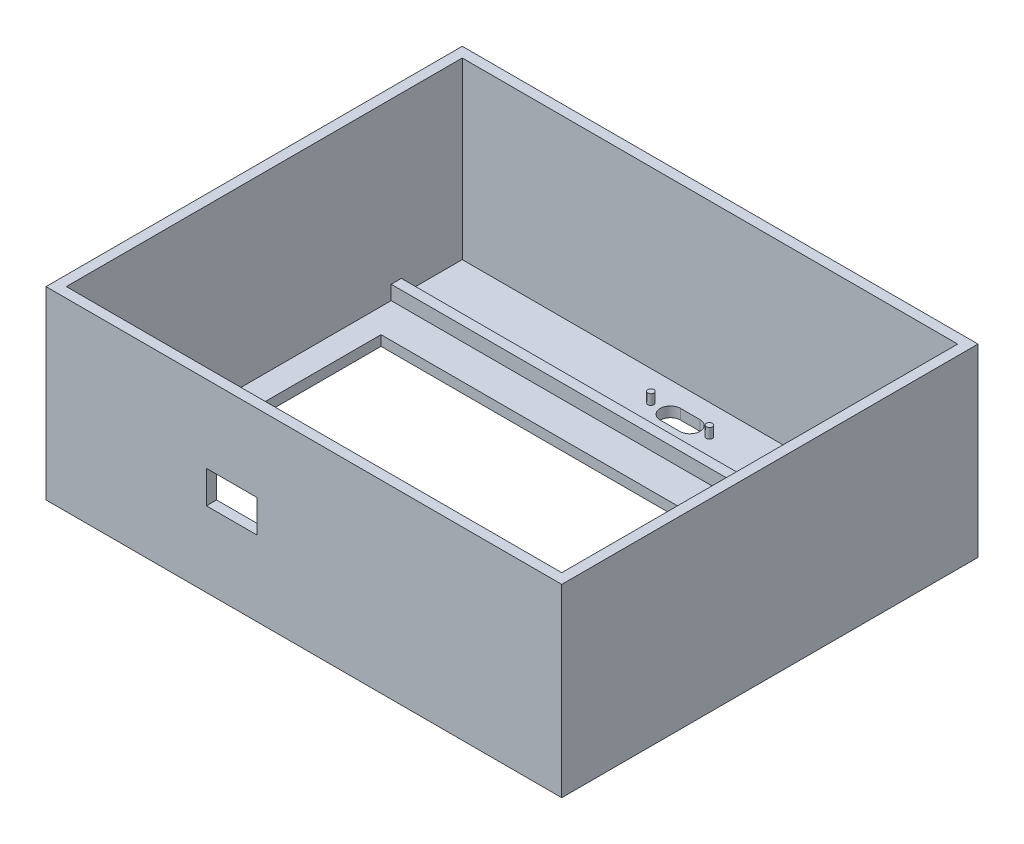
SolidWorks part; units mm, degrees
ref_plane "Front Plane" through (0, 0, 0) normal (0, 0, 1) x (1, 0, 0)
ref_plane "Top Plane" through (0, 0, 0) normal (0, 1, 0) x (1, 0, 0)
ref_plane "Right Plane" through (0, 0, 0) normal (1, 0, 0) x (0, 0, -1)
sketch "Sketch1" plane through (0, 0, 0) normal (0, 1, 0) x (1, 0, 0)
  line L1 (0, 0) -> (127, 0)
  line L2 (0, 0) -> (0, 85)
  line L3 (0, 85) -> (127, 85)
  line L4 (127, 0) -> (127, 85)
extrude "Boss-Extrude1" add sketch "Sketch1" along normal blind 2.5
sketch "Sketch2" plane through (0, 2.5, 0) normal (0, 1, 0) x (1, 0, 0)
  line L0 (0, 85) -> (127, 85)
  line L1 (127, 85) -> (127, 0)
  line L2 (127, 0) -> (0, 0)
  line L3 (0, 0) -> (0, 85)
  line L5 (2.5, 82.5) -> (124.5, 82.5)
  line L6 (2.5, 82.5) -> (2.5, 2.5)
  line L7 (2.5, 2.5) -> (124.5, 2.5)
  line L8 (124.5, 82.5) -> (124.5, 2.5)
  dimension "D1" = 2.5
  dimension "D2" = 2.5
  dimension "D3" = 2.5
  dimension "D4" = 2.5
extrude "Boss-Extrude2" add sketch "Sketch2" along normal blind 38.5
sketch "Sketch3" plane through (0, 0, 0) normal (0, -1, 0) x (-1, 0, 0)
  line L0 (-127, 85) -> (0, 85) construction
  line L1 (-8.5, 5.5) -> (-118.5, 5.5)
  line L2 (-8.5, 5.5) -> (-8.5, 74)
  line L3 (-8.5, 74) -> (-118.5, 74)
  line L4 (-118.5, 5.5) -> (-118.5, 74)
  line L6 (0, 0) -> (-127, 0) construction
  line L7 (-127, 0) -> (-127, 85) construction
  line L8 (0, 85) -> (0, 0) construction
  dimension "D1" = 11
  dimension "D2" = 5.5
  dimension "D3" = 8.5
  dimension "D4" = 8.5
extrude "Cut-Extrude1" cut sketch "Sketch3" against normal blind 2.5
sketch "Sketch6" plane through (0, 0, 0) normal (0, -1, 0) x (-1, 0, 0)
  line L8 (-61.1, 92.6537) -> (-65.9, 92.6537) construction
  line L9 (-61.1, 90.1537) -> (-65.9, 90.1537)
  line L10 (-61.1, 95.1537) -> (-65.9, 95.1537)
  arc A0 (-61.1, 90.1537) -> (-61.1, 95.1537) centre (-61.1, 92.6537) ccw
  arc A2 (-65.9, 95.1537) -> (-65.9, 90.1537) centre (-65.9, 92.6537) ccw
  point P1 (-63.5, 92.6537)
sketch "Sketch9" plane through (0, 0, -85) normal (0, 0, -1) x (-1, 0, 0)
  line L0 (-127, 0) -> (0, 0) construction
  line L1 (-127, 0) -> (0, 0)
  line L2 (-127, 0) -> (-127, 2.5)
  line L4 (0, 0) -> (0, 2.5)
  line L5 (-127, 41) -> (-127, 0) construction
  line L6 (0, 41) -> (0, 0) construction
  line L7 (-2.5, 2.5) -> (-124.5, 2.5)
  line L8 (-127, 41) -> (-124.5, 41)
  line L9 (-127, 41) -> (-127, 2.5)
  line L11 (-124.5, 41) -> (-124.5, 2.5)
  line L12 (0, 41) -> (-2.5, 41)
  line L13 (0, 41) -> (0, 2.5)
  line L15 (-2.5, 41) -> (-2.5, 2.5)
  dimension "D2" = 2.5
  dimension "D3" = 2.5
extrude "Boss-Extrude3" add sketch "Sketch9" along normal blind 15
sketch "Sketch10" plane through (0, 41, 0) normal (0, 1, 0) x (1, 0, 0)
  line L1 (2.5, 85) -> (124.5, 85)
  line L2 (2.5, 85) -> (2.5, 82.5)
  line L3 (2.5, 82.5) -> (124.5, 82.5)
  line L4 (124.5, 85) -> (124.5, 82.5)
extrude "Cut-Extrude2" cut sketch "Sketch10" against normal blind 35
sketch "Sketch11" plane through (0, 0, -100) normal (0, 0, -1) x (-1, 0, 0)
  line L1 (0, 0) -> (-127, 0)
  line L2 (0, 0) -> (0, 41)
  line L3 (0, 41) -> (-127, 41)
  line L4 (-127, 0) -> (-127, 41)
extrude "Boss-Extrude4" add sketch "Sketch11" along normal blind 2.5
sketch "Sketch13" plane through (0, 2.5, 0) normal (0, 1, 0) x (1, 0, 0)
  circle A0 centre (56.3, 92.6537) radius 0.75
  circle A1 centre (70.7, 92.6537) radius 0.75
  arc A2 (61.1, 95.1537) -> (61.1, 90.1537) centre (61.1, 92.6537) ccw construction
  dimension "D1" = 14.4
  dimension "D2" = 4.8
  dimension "D3" = 4.8
  dimension "D4" = 1.5
  dimension "D5" = 1.5
extrude "Cut-Extrude4" cut sketch "Sketch6" against normal blind 2.5
sketch "Sketch14" plane through (0, 2.5, 0) normal (0, 1, 0) x (1, 0, 0)
  line L1 (56, 87.1537) -> (71, 87.1537)
  line L2 (56, 87.1537) -> (56, 86.1537)
  line L3 (56, 86.1537) -> (71, 86.1537)
  line L4 (71, 87.1537) -> (71, 86.1537)
  arc A0 (61.1, 95.1537) -> (61.1, 90.1537) centre (61.1, 92.6537) ccw construction
  arc A1 (65.9, 90.1537) -> (65.9, 95.1537) centre (65.9, 92.6537) ccw construction
  dimension "D1" = 5.1
  dimension "D2" = 5.1
extrude "Cut-Extrude5" cut sketch "Sketch14" against normal blind 1.5
extrude "Boss-Extrude6" add sketch "Sketch13" along normal blind 2.5
sketch "Sketch17" plane through (0, 0, 0) normal (0, 0, 1) x (1, 0, 0)
  line L0 (0, 41) -> (0, 0) construction
  line L1 (39.5, 26.5) -> (52, 26.5)
  line L2 (39.5, 26.5) -> (39.5, 18.5)
  line L3 (39.5, 18.5) -> (52, 18.5)
  line L4 (52, 26.5) -> (52, 18.5)
  line L5 (0, 0) -> (127, 0) construction
  dimension "D1" = 39.5
  dimension "D2" = 18.5
  dimension "D3" = 8
  dimension "D4" = 12.5
extrude "Cut-Extrude6" cut sketch "Sketch17" against normal blind 2.5
sketch "Sketch19" plane through (0, 41, 0) normal (0, 1, 0) x (1, 0, 0)
  line L0 (0, 102.5) -> (127, 102.5)
  line L1 (127, 102.5) -> (127, 0)
  line L2 (127, 0) -> (0, 0)
  line L3 (0, 0) -> (0, 102.5)
  line L5 (2.5, 100) -> (124.5, 100)
  line L6 (2.5, 100) -> (2.5, 2.5)
  line L7 (2.5, 2.5) -> (124.5, 2.5)
  line L8 (124.5, 100) -> (124.5, 2.5)
extrude "Boss-Extrude7" add sketch "Sketch19" along normal blind 4.5
